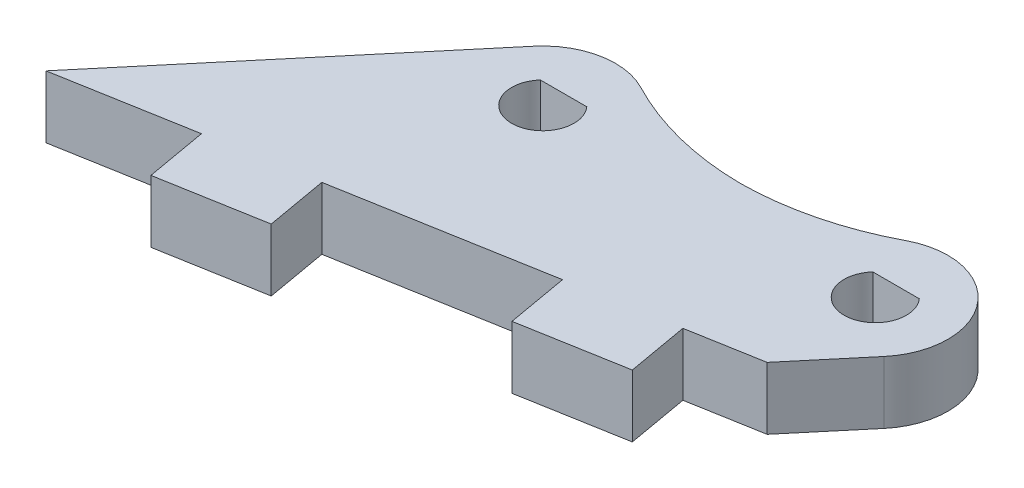
SolidWorks part; units mm, degrees
ref_plane "前视基准面" through (0, 0, 0) normal (0, 0, 1) x (1, 0, 0)
ref_plane "上视基准面" through (0, 0, 0) normal (0, 1, 0) x (1, 0, 0)
ref_plane "右视基准面" through (0, 0, 0) normal (1, 0, 0) x (0, 0, -1)
other "Configuration Table"
sketch "草图2" plane through (0, 0, 0) normal (0, 1, 0) x (1, 0, 0)
  line L14 (-12.8377, 1.5) -> (-3.1623, 1.5)
  line L15 (-16, 0) -> (0, 0) construction
  line L16 (2.6812, -2.2498) -> (0.11, -5.3139)
  line L17 (2.6812, -2.2498) -> (0, 0) construction
  line L18 (0.11, -5.3139) -> (-29.393, -10.5161)
  line L19 (-18.6812, 2.2498) -> (-29.393, -10.5161)
  line L20 (0, 0) -> (0, -3.5) construction
  circle A14 centre (0, 0) radius 1.5
  circle A15 centre (0, 0) radius 3.5
  circle A16 centre (-16, 0) radius 1.5
  circle A17 centre (-16, 0) radius 3.5
  dimension "D1" = 3
  dimension "D2" = 2
  dimension "D3" = 16
  dimension "D5" = 1.5
  dimension "D6" = 140
  dimension "D4" = 100
  dimension "D7" = 4
extrude "凸台-拉伸1" add sketch "草图2" along normal blind 3 contours A17 A16 | A15 A14 | A17 L19 L18 L16 A15 L14 region at (-13.6148, 0, 4.2858) region at (-12.6821, 0, -0.747) region at (0.747, 0, -3.3179)
fillet "圆角1" radius 14 2 edges at (-3.1623, 1.5, -1.5) (-12.8377, 1.5, -1.5)
sketch "草图3" plane through (0.9121, 0, 5.1725) normal (0.1736, 0, 0.9848) x (0.9848, 0, -0.1736)
  line L0 (-30.7725, 3) -> (-30.7725, 0) construction
  line L1 (-0.8144, 3) -> (-0.8144, 0) construction
  line L2 (-0.8144, 3) -> (-30.7725, 3) construction
  line L3 (-24.3144, 0) -> (-19.3144, 0)
  line L4 (-24.3144, 0) -> (-24.3144, 3)
  line L5 (-24.3144, 3) -> (-19.3144, 3)
  line L6 (-19.3144, 0) -> (-19.3144, 3)
  line L7 (-24.3144, 0) -> (-19.3144, 3) construction
  line L8 (-24.3144, 3) -> (-19.3144, 0) construction
  line L10 (-4.3144, 0) -> (-9.3144, 0)
  line L11 (-4.3144, 0) -> (-4.3144, 3)
  line L12 (-4.3144, 3) -> (-9.3144, 3)
  line L13 (-9.3144, 0) -> (-9.3144, 3)
  line L14 (-4.3144, 0) -> (-9.3144, 3) construction
  line L15 (-4.3144, 3) -> (-9.3144, 0) construction
  circle A0 centre (-21.8144, 1.5) radius 0.4 construction
  circle A1 centre (-6.8144, 1.5) radius 0.4 construction
  point P6 (-30.7725, 1.5)
  dimension "D1" = 0.8
  dimension "D2" = 6
  dimension "D3" = 15
  dimension "D4" = 5
extrude "凸台-拉伸2" add sketch "草图3" along normal blind 3
sketch "草图5" plane through (0, 0, 0) normal (0, -1, 0) x (1, 0, 0)
  line L0 (1.118, -1) -> (-1.118, -1)
  line L1 (-14.882, -1) -> (-17.118, -1)
  circle A0 centre (0, 0) radius 1.5 construction
  circle A1 centre (-16, 0) radius 1.5 construction
  circle A2 centre (0, 0) radius 1.5
  circle A3 centre (-16, 0) radius 1.5
  circle M3 centre (-16, 0) radius 1.5
  circle M19 centre (0, 0) radius 1.5
  dimension "D1" = 1
extrude "凸台-拉伸4" add sketch "草图5" against normal up to surface (3 mm away) contours L1 M3 | L0 M19 region at (0, 0, -1.2032) region at (-16, 0, -1.2032) up to face at (-16, 3, 1.5)
